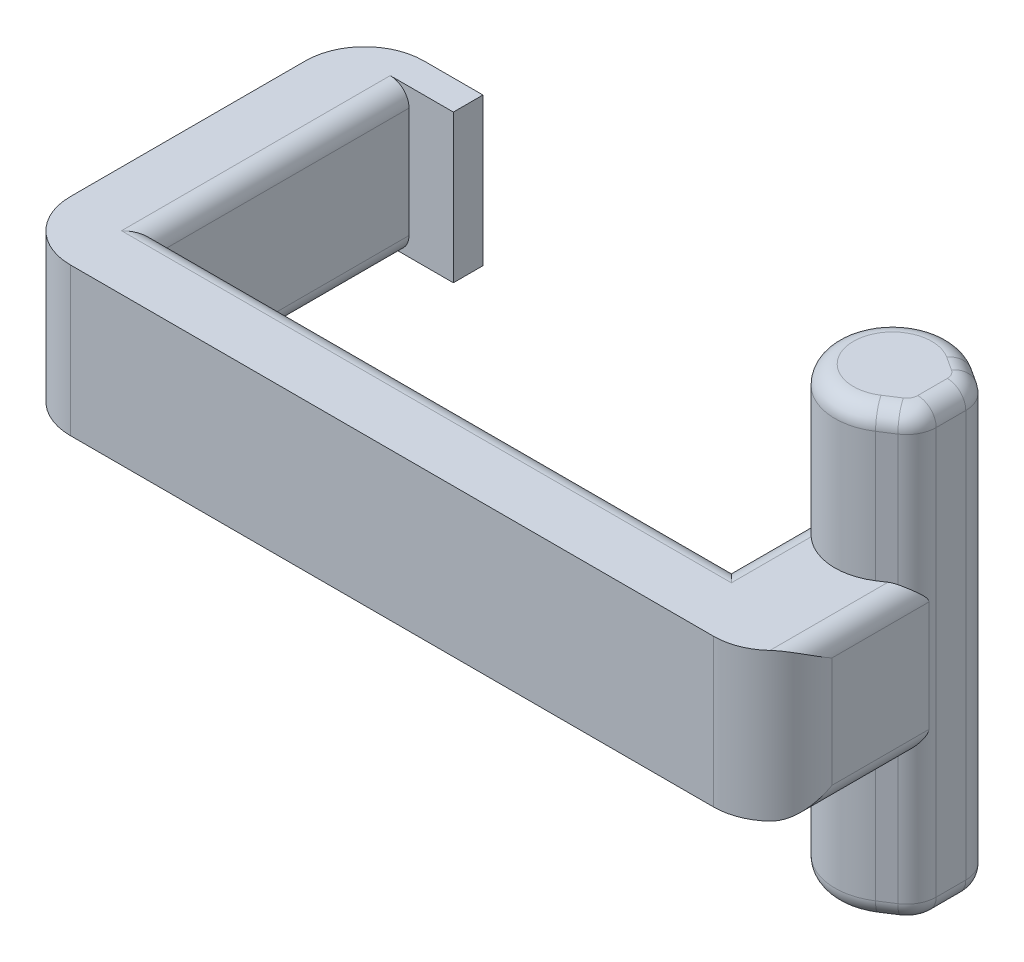
SolidWorks part; units mm, degrees
ref_plane "Front Plane" through (0, 0, 0) normal (1, 0, 0) x (0, 1, 0)
ref_plane "Top Plane" through (0, 0, 0) normal (0, 0, 1) x (0, 1, 0)
ref_plane "Right Plane" through (0, 0, 0) normal (0, 1, 0) x (-1, 0, 0)
sketch "Sketch1" plane through (0, 0, 0) normal (0, 1, 0) x (-1, 0, 0)
  circle A0 centre (0, 0) radius 4.953
  dimension "D1" = 9.906
extrude "Boss-Extrude1" add sketch "Sketch1" along normal mid plane 38.1
sketch "Sketch3" plane through (0, 0, 0) normal (0, 1, 0) x (-1, 0, 0)
  line L0 (-4.953, 0) -> (-4.953, 15.24)
  line L1 (-4.953, 15.24) -> (60.452, 15.24)
  line L2 (60.452, 15.24) -> (60.452, -15.113)
  line L3 (60.452, -15.113) -> (50.292, -15.113)
  line L4 (50.292, -15.113) -> (50.292, -12.573)
  line L5 (50.292, -12.573) -> (54.102, -12.573)
  line L6 (54.102, -12.573) -> (54.102, 8.89)
  line L7 (54.102, 8.89) -> (4.953, 8.89)
  line L8 (4.953, 8.89) -> (4.953, 0)
  line L9 (-4.953, 0) -> (-4.953, -15.113) construction
  line L10 (-4.953, -15.113) -> (50.292, -15.113) construction
  line L11 (54.102, 15.24) -> (54.102, 8.89) construction
  line L12 (60.452, 8.89) -> (54.102, 8.89) construction
  line L13 (-4.953, 0) -> (4.953, 0) construction
  line L14 (-4.953, -15.113) -> (-8.763, -15.113) construction
  line L15 (-8.763, -15.113) -> (-8.763, 15.24) construction
  line L16 (-8.763, 15.24) -> (-4.953, 15.24) construction
  line L17 (0, -4.953) -> (0, -15.113) construction
  line L18 (0, 0) -> (50.292, -12.573) construction
  line L19 (0, 0) -> (50.292, -15.113) construction
  line L20 (50.292, -15.113) -> (50.292, -17.78) construction
  line L21 (50.292, -17.78) -> (60.452, -17.78) construction
  line L22 (60.452, -17.78) -> (60.452, -15.113) construction
  circle A0 centre (0, 0) radius 4.953 construction
  circle A2 centre (0, 0) radius 4.953
  arc A3 (-4.953, 0) -> (4.953, 0) centre (0, 0) ccw
  dimension "D1" = 8.89
  dimension "D2" = 2.54
  dimension "D3" = 3.81
  dimension "D4" = 90
  dimension "D5" = 6.35
  dimension "D7" = 69.215
  dimension "D8" = 3.81
  dimension "D9" = 10.16
  dimension "D6" = 0
extrude "Boss-Extrude2" add sketch "Sketch3" along normal mid plane 12.7 contours L0 A3 L8 L7 L6 L5 L4 L20 L21 L22 L2 L1
fillet "Fillet1" radius 5.08 3 edges at (-60.452, 0, -15.113) (-60.452, 0, 15.24) (4.953, 0, 15.24)
sketch "Sketch4" plane through (0, -19.05, 0) normal (0, -1, 0) x (1, 0, 0)
  line L0 (5.0165, 1.27) -> (5.0165, -1.27)
  line L1 (3.8585, -3.4011) -> (2.6949, -4.1557)
  line L2 (3.8585, 3.4011) -> (2.6949, 4.1557)
  line L3 (0, 0) -> (5.0165, 0) construction
  line L4 (2.6949, 4.1557) -> (2.6949, -4.1557)
  line L5 (-3.6707, 3.5118) -> (3.6707, -3.5118) construction
  circle A0 centre (0, 0) radius 5.08 construction
  circle A1 centre (0, 0) radius 4.953 construction
  arc A2 (3.8585, -3.4011) -> (5.0165, -1.27) centre (2.4765, -1.27) ccw
  arc A3 (5.0165, 1.27) -> (3.8585, 3.4011) centre (2.4765, 1.27) ccw
  point P12 (0, 0)
  point P17 (0, 0)
  dimension "D1" = 2.54
  dimension "D4" = 10.16
  dimension "D2" = 5.0165
  dimension "D3" = 2.54
extrude "Boss-Extrude3" add sketch "Sketch4" against normal up to surface (38.1 mm away) up to face at (0, 19.05, 4.953)
fillet "Fillet2" radius 1.5875 12 edges at (3.2767, -19.05, -3.7784) (4.7083, -19.05, -2.4827) (5.0165, -19.05, 0) (4.7083, -19.05, 2.4827) (3.2767, -19.05, 3.7784) (3.2767, 19.05, -3.7784) (4.7083, 19.05, -2.4827) (5.0165, 19.05, 0) (4.7083, 19.05, 2.4827) (3.2767, 19.05, 3.7784) (-4.953, 19.05, 0) (-4.953, -19.05, 0)
fillet "Fillet3" radius 1.6129 8 edges at (-54.102, -6.35, -1.8415) (-54.102, 6.35, -1.8415) (-29.5275, -6.35, 8.89) (-29.5275, 6.35, 8.89) (-4.953, 6.35, 4.445) (-4.953, -6.35, 4.445) (4.953, 6.35, 5.9972) (4.953, -6.35, 5.9972)
